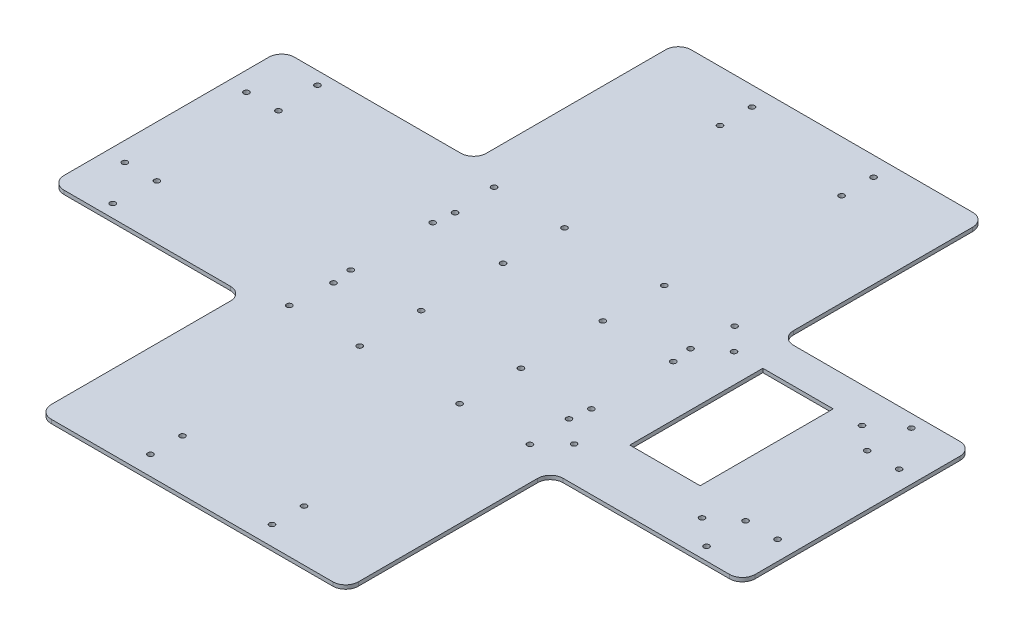
SolidWorks part; units mm, degrees
ref_plane "Front Plane" through (0, 0, 0) normal (0, 0, 1) x (1, 0, 0)
ref_plane "Top Plane" through (0, 0, 0) normal (0, 1, 0) x (1, 0, 0)
ref_plane "Right Plane" through (0, 0, 0) normal (1, 0, 0) x (0, 0, -1)
sketch "Sketch1" plane through (0, 0, 0) normal (0, 1, 0) x (1, 0, 0)
  line L0 (120, 250) -> (-120, 250)
  line L1 (-120, 250) -> (-120, 90)
  line L2 (-120, 90) -> (-270, 90)
  line L3 (-270, 90) -> (-270, -90)
  line L4 (0, 319.0603) -> (0, -214.0477) construction
  line L5 (-295.2994, 0) -> (181.6639, 0) construction
  line L6 (270, 90) -> (270, -90)
  line L7 (120, 90) -> (270, 90)
  line L8 (120, 250) -> (120, 90)
  line L9 (120, -250) -> (120, -90)
  line L10 (120, -90) -> (270, -90)
  line L11 (-120, -90) -> (-270, -90)
  line L12 (-120, -250) -> (-120, -90)
  line L13 (120, -250) -> (-120, -250)
  point P14 (0, 250)
  point P15 (-270, 0)
  point P16 (270, 0)
  point P20 (0, -250)
  dimension "D1" = 120
  dimension "D2" = 160
  dimension "150" = 150
  dimension "D3" = 90
extrude "Base" add sketch "Sketch1" along normal blind 3
fillet "Fillet1" radius 10 12 edges at (120, 1.5, -90) (270, 1.5, -90) (270, 1.5, 90) (120, 1.5, 90) (120, 1.5, 250) (-120, 1.5, 250) (-120, 1.5, 90) (-270, 1.5, 90) (-270, 1.5, -90) (-120, 1.5, -90) (-120, 1.5, -250) (120, 1.5, -250)
sketch "Sketch2" plane through (0, 3, 0) normal (0, 1, 0) x (1, 0, 0)
  line L0 (0, 268.1887) -> (0, -286.5172) construction
  line L1 (-278.1616, 0) -> (318.0529, 0) construction
  line L2 (110, 250) -> (-110, 250) construction
  line L3 (-270, 80) -> (-270, -80) construction
  circle A0 centre (-47.5, 235) radius 2.125
  circle A1 centre (-47.5, 210) radius 2.125
  circle A2 centre (-255, 47.5) radius 2.125
  circle A3 centre (-230, 47.5) radius 2.125
  circle A4 centre (-230, -47.5) radius 2.125
  circle A5 centre (-255, -47.5) radius 2.125
  circle A6 centre (255, -47.5) radius 2.125
  circle A7 centre (230, -47.5) radius 2.125
  circle A8 centre (230, 47.5) radius 2.125
  circle A9 centre (255, 47.5) radius 2.125
  circle A10 centre (47.5, 210) radius 2.125
  circle A11 centre (47.5, 235) radius 2.125
  circle A12 centre (47.5, -235) radius 2.125
  circle A13 centre (47.5, -210) radius 2.125
  circle A14 centre (-47.5, -210) radius 2.125
  circle A15 centre (-47.5, -235) radius 2.125
  dimension "D1" = 4.25
  dimension "D2" = 4.25
  dimension "D3" = 4.25
  dimension "D4" = 4.25
  dimension "D5" = 47.5
  dimension "D6" = 25
  dimension "D7" = 15
  dimension "D8" = 25
  dimension "D9" = 15
  dimension "D10" = 47.5
extrude "Armor Module Holes" cut sketch "Sketch2" against normal blind 3
sketch "Sketch3" plane through (0, 3, 0) normal (0, 1, 0) x (1, 0, 0)
  line L0 (-268.1887, 0) -> (424.969, 0) construction
  line L1 (0, 281.6655) -> (0, -321.0178) construction
  line L2 (-149.3232, 150) -> (229.1059, 150) construction
  line L3 (-149.3232, -150) -> (229.1059, -150) construction
  circle A0 centre (92, 47.5) radius 2.125
  circle A1 centre (92, -47.5) radius 2.125
  circle A2 centre (-92, -47.5) radius 2.125
  circle A3 centre (-92, 47.5) radius 2.125
  dimension "D2" = 4.25
  dimension "D1" = 150
  dimension "D3" = 47.5
  dimension "D4" = 92
extrude "Plates for Gimbal" cut sketch "Sketch3" against normal blind 3
sketch "Sketch6" plane through (0, 3, 0) normal (0, 1, 0) x (1, 0, 0)
  line L0 (-219.2229, 0) -> (231.3521, 0) construction
  line L1 (52.5596, 72.5) -> (282.564, 72.5) construction
  line L2 (52.5596, -72.5) -> (333.7759, -72.5) construction
  line L3 (92, 47.5) -> (230, 47.5) construction
  line L4 (161, 96.4976) -> (161, -82.3612) construction
  line L6 (133.5, 62.5) -> (188.5, 62.5)
  line L7 (133.5, 62.5) -> (133.5, -41.5)
  line L8 (133.5, -41.5) -> (188.5, -41.5)
  line L9 (188.5, 62.5) -> (188.5, -41.5)
  circle A2 centre (111, -62.5) radius 2.125
  circle A4 centre (211, -62.5) radius 2.125
  circle A5 centre (211, 62.5) radius 2.125
  circle A6 centre (111, 62.5) radius 2.125
  dimension "D3" = 10
  dimension "D4" = 50
  dimension "D6" = 4.25
  dimension "D1" = 72.5
  dimension "D2" = 72.5
  dimension "D9" = 69
  dimension "D12" = 55
  dimension "D13" = 27.5
  dimension "D14" = 10
  dimension "D15" = 104
extrude "Battery Mount" cut sketch "Sketch6" against normal blind 10
sketch "Sketch5" plane through (0, 3, 0) normal (0, 1, 0) x (1, 0, 0)
  line L0 (0, 63.8605) -> (0, -71.0696) construction
  line L1 (-72.0204, 0) -> (84.8823, 0) construction
  line L2 (120, -240) -> (120, -100) construction
  line L3 (-110, -250) -> (110, -250) construction
  line L4 (-158.9191, 72.5) -> (235.5165, 72.5) construction
  line L5 (188.5, 62.5) -> (133.5, 62.5) construction
  circle A0 centre (94, -32) radius 2.125
  circle A1 centre (94, -80) radius 2.125
  circle A2 centre (39, -32) radius 2.125
  circle A3 centre (39, -80) radius 2.125
  circle A4 centre (-39, -80) radius 2.125
  circle A5 centre (-39, -32) radius 2.125
  circle A6 centre (-94, -80) radius 2.125
  circle A7 centre (-94, -32) radius 2.125
  circle A8 centre (-94, 32) radius 2.125
  circle A9 centre (-94, 80) radius 2.125
  circle A10 centre (-39, 32) radius 2.125
  circle A11 centre (-39, 80) radius 2.125
  circle A12 centre (39, 80) radius 2.125
  circle A13 centre (39, 32) radius 2.125
  circle A14 centre (94, 80) radius 2.125
  circle A15 centre (94, 32) radius 2.125
  dimension "D1" = 4.25
  dimension "D2" = 4.25
  dimension "D5" = 4.25
  dimension "D6" = 4.25
  dimension "D9" = 10
  dimension "D3" = 48
  dimension "D4" = 26
  dimension "D7" = 55
  dimension "D8" = 170
extrude "Suspension Mount" cut sketch "Sketch5" against normal blind 10
sketch "Sketch7" plane through (0, 3, 0) normal (0, 1, 0) x (1, 0, 0)
  line L0 (-234.9459, 0) -> (256.0596, 0) construction
  line L1 (0, 229.7798) -> (0, -225.7367) construction
  line L2 (-120, -100) -> (-120, -240) construction
  circle A0 centre (-232, -80) radius 2.125
  circle A1 centre (-232, 80) radius 2.125
  circle A2 centre (232, 80) radius 2.125
  circle A3 centre (232, -80) radius 2.125
  dimension "D1" = 4.25
  dimension "D2" = 80
  dimension "D3" = 112
extrude "Cut-Extrude1" cut sketch "Sketch7" against normal blind 10
